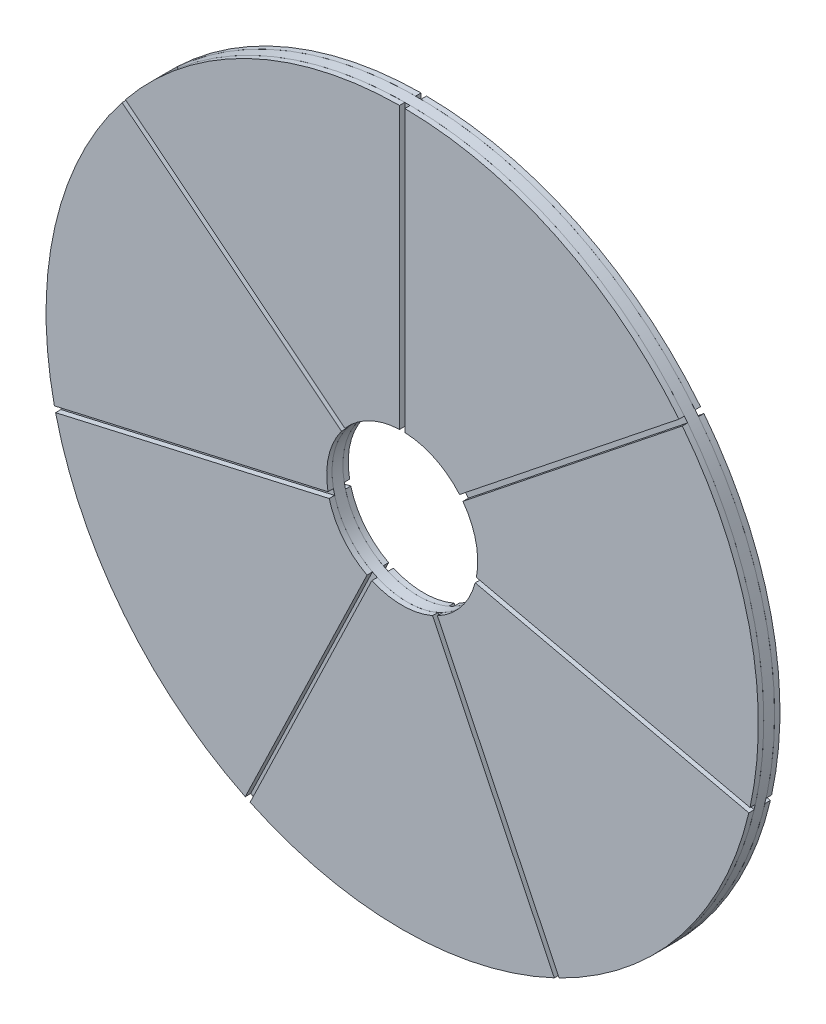
SolidWorks part; units mm, degrees
ref_plane "Front Plane" through (0, 0, 0) normal (0, 0, 1) x (1, 0, 0)
ref_plane "Top Plane" through (0, 0, 0) normal (0, 1, 0) x (1, 0, 0)
ref_plane "Right Plane" through (0, 0, 0) normal (1, 0, 0) x (0, 0, -1)
sketch "Sketch1" plane through (0, 0, 0) normal (0, 0, 1) x (1, 0, 0)
  circle A0 centre (0, 0) radius 16.5
  dimension "D1" = 33
extrude "Boss-Extrude1" add sketch "Sketch1" along normal blind 0.25 and the other way blind 0.25 contours A0
sketch "Sketch2" plane through (0, 0, 0.25) normal (0, 0, 1) x (1, 0, 0)
  line L0 (-0.0779, 0.0977) -> (0.0779, -0.0977)
  line L1 (-0.125, 0) -> (0.125, 0)
  line L2 (-0.125, 0) -> (-0.125, 19.4123)
  line L3 (-0.125, 19.4123) -> (0.125, 19.4123)
  line L4 (0.125, 0) -> (0.125, 19.4123)
  line L5 (-0.0779, 0.0977) -> (15.0992, 12.2011)
  line L6 (15.0992, 12.2011) -> (15.255, 12.0056)
  line L7 (0.0779, -0.0977) -> (15.255, 12.0056)
  line L8 (0.0278, 0.1219) -> (-0.0278, -0.1219)
  line L9 (0.0278, 0.1219) -> (18.9534, -4.1978)
  line L10 (18.9534, -4.1978) -> (18.8977, -4.4415)
  line L11 (-0.0278, -0.1219) -> (18.8977, -4.4415)
  line L12 (0.1126, 0.0542) -> (-0.1126, -0.0542)
  line L13 (0.1126, 0.0542) -> (8.5353, -17.4356)
  line L14 (8.5353, -17.4356) -> (8.31, -17.5441)
  line L15 (-0.1126, -0.0542) -> (8.31, -17.5441)
  line L16 (0.1126, -0.0542) -> (-0.1126, 0.0542)
  line L17 (0.1126, -0.0542) -> (-8.31, -17.5441)
  line L18 (-8.31, -17.5441) -> (-8.5353, -17.4356)
  line L19 (-0.1126, 0.0542) -> (-8.5353, -17.4356)
  line L20 (0.0278, -0.1219) -> (-0.0278, 0.1219)
  line L21 (0.0278, -0.1219) -> (-18.8977, -4.4415)
  line L22 (-18.8977, -4.4415) -> (-18.9534, -4.1978)
  line L23 (-0.0278, 0.1219) -> (-18.9534, -4.1978)
  line L24 (-0.0779, -0.0977) -> (0.0779, 0.0977)
  line L25 (-0.0779, -0.0977) -> (-15.255, 12.0056)
  line L26 (-15.255, 12.0056) -> (-15.0992, 12.2011)
  line L27 (0.0779, 0.0977) -> (-15.0992, 12.2011)
  circle A0 centre (0, 0) radius 19
  point P7 (0, 0)
  point P15 (0, 0)
  point P19 (0, 0)
  point P21 (0, 0)
  point P26 (0, 0)
  point P31 (0, 0)
  point P36 (0, 0)
  point P41 (0, 0)
  point P42 (0, 0)
  circle M1 centre (0, 0) radius 16.5
  dimension "D1" = 7
  dimension "D2" = 38
extrude "Boss-Extrude2" add sketch "Sketch2" along normal blind 0.25 separate body contours L4 L5 M1 | L27 L2 M1 | L23 L25 M1 | L19 L21 M1 | L15 L17 M1 | L11 L13 M1 | L7 L9 M1 region at (4.661, 9.6786, 0.25) region at (-4.661, 9.6786, 0.25) region at (-10.4731, 2.3904, 0.25) region at (10.4731, 2.3904, 0.25) region at (8.3988, -6.6978, 0.25) region at (0, -10.7424, 0.25) region at (-8.3988, -6.6978, 0.25)
mirror "Mirror5" about plane through (0, 0, 0) normal (0, 0, 1) of bodies 125 124 164 122 120 123 163 104 103 102 141
sketch "Sketch3" plane through (0, 0, 0) normal (0, 0, 1) x (1, 0, 0)
  circle A0 centre (0, 0) radius 3.5
  dimension "D1" = 7
extrude "Cut-Extrude2" cut sketch "Sketch3" against normal blind 8.35 and the other way blind 10 contours A0
